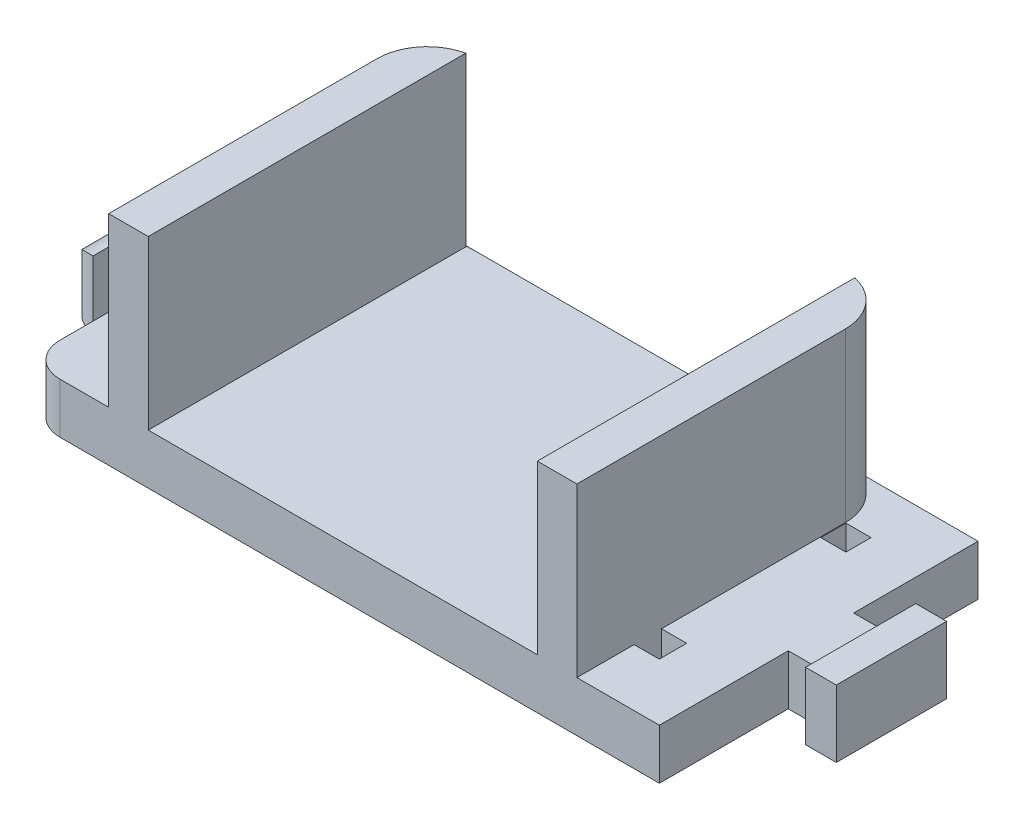
SolidWorks part; units mm, degrees
ref_plane "Front Plane" through (0, 0, 0) normal (0, 0, 1) x (1, 0, 0)
ref_plane "Top Plane" through (0, 0, 0) normal (0, 1, 0) x (1, 0, 0)
ref_plane "Right Plane" through (0, 0, 0) normal (1, 0, 0) x (0, 0, -1)
sketch "Sketch1" plane through (0, 0, 0) normal (0, 1, 0) x (1, 0, 0)
  line L0 (23.8048, 3.5399) -> (-19.4466, 3.5399) construction
  line L1 (-13.9454, 22.5399) -> (23.8048, 22.5399)
  line L2 (-13.9454, 22.5399) -> (-13.9454, -15.4601)
  line L3 (-13.9454, -15.4601) -> (23.8048, -15.4601)
  line L4 (23.8048, 22.5399) -> (23.8048, -15.4601)
  line L5 (-18.6768, -0.0823) -> (-13.9454, -0.0823)
  line L6 (-7.1952, 16.5399) -> (-4.1952, 16.5399)
  line L7 (-7.1952, 16.5399) -> (-7.1952, 13.5399)
  line L8 (-7.1952, 13.5399) -> (-4.1952, 13.5399)
  line L9 (-4.1952, 16.5399) -> (-4.1952, 13.5399)
  line L10 (-7.1173, -5.371) -> (-4.1152, -5.371)
  line L11 (-7.1173, -5.371) -> (-7.1173, -8.642)
  line L12 (-7.1173, -8.642) -> (-4.1152, -8.642)
  line L13 (-4.1152, -5.371) -> (-4.1152, -8.642)
  line L14 (-18.6768, -0.0823) -> (-18.6768, 7.7131)
  line L15 (-13.9454, -0.0823) -> (-13.9454, 7.7131)
  line L16 (-18.6768, 7.7131) -> (-13.9454, 7.7131)
  line L17 (-13.9454, 3.8154) -> (-18.6768, 3.8154) construction
  line L18 (-16.3111, -0.0823) -> (-16.3111, 7.7131) construction
  line L19 (-22.3476, 10.3921) -> (-18.6768, 10.3921)
  line L20 (-22.3476, 10.3921) -> (-22.3476, -2.7613)
  line L21 (-18.6768, 10.3921) -> (-18.6768, -2.7613)
  line L22 (-22.3476, -2.7613) -> (-18.6768, -2.7613)
  line L23 (-18.6768, 3.8154) -> (-22.3476, 3.8154) construction
  line L24 (-20.5122, 10.3921) -> (-20.5122, -2.7613) construction
  point P10 (-4.1952, 15.0399)
  point P15 (-3.9708, 15.8169)
  point P16 (-16.3111, 3.8154)
  point P17 (-20.5122, 3.8154)
  point P18 (0, 0)
  point P23 (-7.1952, 13.5399)
  dimension "D1" = 28
  dimension "D2" = 6
  dimension "D3" = 38
extrude "Boss-Extrude1" add sketch "Sketch1" along normal blind 6 contours L4 L1 L2 L3 L6 L9 L8 L7 L10 L13 L12 L11 | L16 L14 L5 L2 | L20 L22 L21 L14 L19 region at (5.0704, 0, -3.54) region at (-16.3111, 0, -3.8154) region at (-20.5122, 0, -3.8154)
sketch "Sketch2" plane through (0, 6, 0) normal (0, 1, 0) x (1, 0, 0)
  line L0 (-13.9454, 22.5399) -> (23.8048, 22.5399) construction
  line L1 (-4.1152, 22.5399) -> (0.6048, 22.5399)
  line L2 (-4.1152, 22.5399) -> (-4.1152, -15.4601)
  line L3 (-4.1152, -15.4601) -> (0.6048, -15.4601)
  line L4 (0.6048, 22.5399) -> (0.6048, -15.4601)
  line L5 (-13.9454, -15.4601) -> (23.8048, -15.4601) construction
  line L8 (-4.1152, -5.371) -> (-4.1152, -8.642) construction
  dimension "D1" = 23.2
extrude "Boss-Extrude2" add sketch "Sketch2" along normal blind 20 contours L2 L1 L4 L3
fillet "Fillet1" radius 6 1 edges at (-4.1152, 16, -22.5399)
sketch "Sketch3" plane through (0, 6, 0) normal (0, 1, 0) x (1, 0, 0)
  line L0 (-18.6768, 10.3921) -> (-18.6768, 7.7131) construction
  line L1 (-18.6768, 10.3921) -> (-22.3476, 10.3921)
  line L2 (-18.6768, 10.3921) -> (-18.6768, -2.7613)
  line L3 (-18.6768, -2.7613) -> (-22.3476, -2.7613)
  line L4 (-22.3476, 10.3921) -> (-22.3476, -2.7613)
  point P7 (-18.6768, 10.3921)
extrude "Boss-Extrude3" add sketch "Sketch3" along normal blind 2
mirror "Mirror1" about plane through (23.8048, 6, 0) normal (1, 0, 0) of "Boss-Extrude1", "Boss-Extrude2", "Fillet1", "Boss-Extrude3"
fillet "Fillet2" radius 4 5 edges at (-13.9454, 3, 15.4601) (-13.9454, 3, -22.5399) (-22.3476, 4, 2.7613) (-22.3476, 8, -3.8154) (-22.3476, 4, -10.3921)
